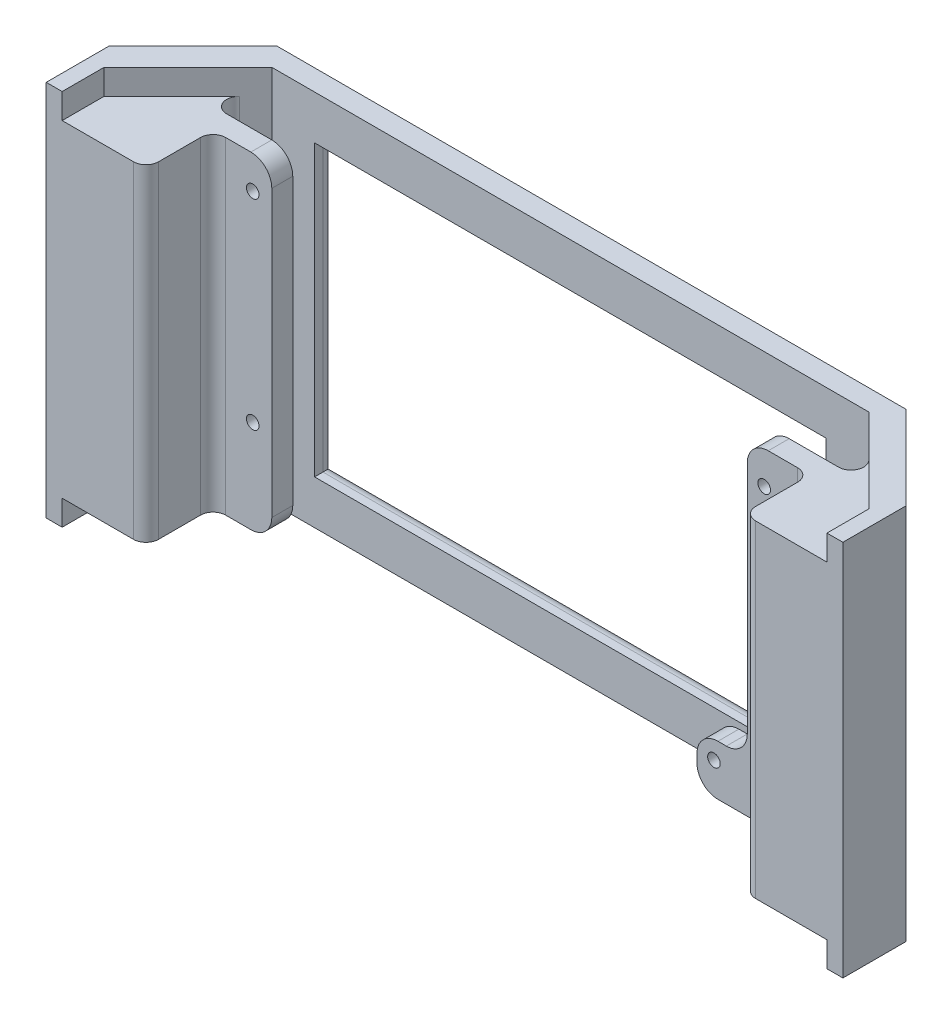
SolidWorks part; units mm, degrees
ref_plane "Front Plane" through (0, 0, 0) normal (0, 0, 1) x (1, 0, 0)
ref_plane "Top Plane" through (0, 0, 0) normal (0, 1, 0) x (1, 0, 0)
ref_plane "Right Plane" through (0, 0, 0) normal (1, 0, 0) x (0, 0, -1)
sketch "Sketch1" plane through (0, 0, 0) normal (0, 0, 1) x (1, 0, 0)
  line L1 (-95, 45) -> (95, 45)
  line L2 (-95, 45) -> (-95, -45)
  line L3 (-95, -45) -> (95, -45)
  line L4 (95, 45) -> (95, -45)
  line L5 (-95, 45) -> (95, -45) construction
  line L6 (-95, -45) -> (95, 45) construction
  line L7 (-61, 34.5) -> (61, 34.5)
  line L8 (-61, 34.5) -> (-61, -34.5)
  line L9 (-61, -34.5) -> (61, -34.5)
  line L10 (61, 34.5) -> (61, -34.5)
  line L11 (-61, 34.5) -> (61, -34.5) construction
  line L12 (-61, -34.5) -> (61, 34.5) construction
  point P0 (0, 0)
  point P6 (0, 0)
  dimension "D1" = 122
  dimension "D2" = 190
  dimension "D3" = 69
  dimension "D4" = 90
extrude "Boss-Extrude1" add sketch "Sketch1" along normal blind 5
sketch "Sketch2" plane through (0, 0, 5) normal (0, 0, 1) x (1, 0, 0)
  line L0 (-95, -45) -> (95, -45) construction
  line L1 (-95, 45) -> (-91.2, 45)
  line L2 (-95, 45) -> (-95, -45)
  line L3 (-95, -45) -> (-91.2, -45)
  line L4 (-91.2, 45) -> (-91.2, -45)
  line L5 (0, 0) -> (0, 45) construction
  line L6 (95, 45) -> (-95, 45) construction
  line L7 (95, -45) -> (91.2, -45)
  line L8 (91.2, 45) -> (91.2, -45)
  line L9 (95, 45) -> (91.2, 45)
  line L10 (95, 45) -> (95, -45)
  dimension "D1" = 3.8
extrude "Boss-Extrude2" add sketch "Sketch2" along normal blind 30
sketch "Sketch3" plane through (0, 45, 0) normal (0, 1, 0) x (1, 0, 0)
  line L0 (-91.2, -35) -> (-91.2, -5) construction
  line L1 (-91.2, -14) -> (-57.2, -14)
  line L2 (-91.2, -14) -> (-91.2, -19)
  line L3 (-91.2, -19) -> (-57.2, -19)
  line L4 (-57.2, -14) -> (-57.2, -19)
  line L5 (91.2, -35) -> (91.2, -5) construction
  line L6 (91.2, -14) -> (44.2, -14)
  line L7 (91.2, -14) -> (91.2, -19)
  line L8 (91.2, -19) -> (44.2, -19)
  line L9 (44.2, -14) -> (44.2, -19)
  line L10 (91.2, -5) -> (-91.2, -5) construction
  dimension "D1" = 9
  dimension "D2" = 9
  dimension "D3" = 5
  dimension "D4" = 5
  dimension "D5" = 34
  dimension "D6" = 47
extrude "Boss-Extrude3" add sketch "Sketch3" against normal up to surface (90 mm away) up to face at (0, -45, 18.75)
sketch "Sketch4" plane through (0, 0, 19) normal (0, 0, 1) x (1, 0, 0)
  line L0 (91.2, -45) -> (91.2, 45) construction
  line L1 (-91.2, 45) -> (91.2, 45)
  line L2 (-91.2, 45) -> (-91.2, 39)
  line L3 (-91.2, 39) -> (91.2, 39)
  line L4 (91.2, 45) -> (91.2, 39)
  line L5 (0, 0) -> (-91.2, 0) construction
  line L6 (-91.2, -45) -> (-91.2, 45) construction
  line L7 (-91.2, -39) -> (91.2, -39)
  line L8 (91.2, -45) -> (91.2, -39)
  line L9 (-91.2, -45) -> (91.2, -45)
  line L10 (-91.2, -45) -> (-91.2, -39)
  dimension "D1" = 6
extrude "Cut-Extrude1" cut sketch "Sketch4" against normal blind 5
sketch "Sketch5" plane through (0, 0, 19) normal (0, 0, 1) x (1, 0, 0)
  line L0 (0, 0) -> (-61.75, 0) construction
  line L1 (-70.2, 37.38) -> (70.2, 37.38) construction
  line L2 (-70.2, 37.38) -> (-70.2, -37.38) construction
  line L3 (-70.2, -37.38) -> (70.2, -37.38) construction
  line L4 (70.2, 37.38) -> (70.2, -37.38) construction
  line L5 (-70.2, 37.38) -> (70.2, -37.38) construction
  line L6 (-70.2, -37.38) -> (70.2, 37.38) construction
  line L7 (-61.75, 0) -> (-61.75, 31.13) construction
  line L8 (-61.75, 0) -> (-61.75, -16.61) construction
  line L9 (48.25, 0) -> (60.23, 0) construction
  line L10 (60.23, 0) -> (60.23, 31.13) construction
  line L11 (0, 0) -> (48.25, 0) construction
  line L12 (48.25, 0) -> (48.25, -31.38) construction
  circle A0 centre (-61.75, 31.13) radius 1.5
  circle A1 centre (-61.75, -16.61) radius 1.5
  circle A2 centre (60.23, 31.13) radius 1.5
  circle A3 centre (48.25, -31.38) radius 1.5
  point P0 (0, 0)
  dimension "D10" = 3
  dimension "D11" = 3
  dimension "D12" = 3
  dimension "D13" = 3
  dimension "D1" = 140.4
  dimension "D2" = 74.76
  dimension "D3" = 61.75
  dimension "D4" = 31.13
  dimension "D5" = 16.61
  dimension "D6" = 60.23
  dimension "D7" = 31.13
  dimension "D8" = 48.25
  dimension "D9" = 31.38
extrude "Cut-Extrude2" cut sketch "Sketch5" against normal up to surface (5 mm away) up to face at (67.7, 0, 14)
sketch "Sketch6" plane through (0, 0, 19) normal (0, 0, 1) x (1, 0, 0)
  line L1 (44.2, 39) -> (56.2, 39)
  line L2 (44.2, 39) -> (44.2, -27)
  line L3 (44.2, -27) -> (56.2, -27)
  line L4 (56.2, 39) -> (56.2, -27)
  dimension "D1" = 12
  dimension "D2" = 66
extrude "Cut-Extrude3" cut sketch "Sketch6" against normal up to surface (5 mm away) up to face at (46.75, -31.38, 14)
fillet "Fillet3" radius 3 4 edges at (-61, 0, 0) (0, -34.5, 0) (61, 0, 0) (0, 34.5, 0)
chamfer "Chamfer6" distance 20 angle 45 4 edges at (91.2, 0, 5) (95, 0, 0) (-95, 0, 0) (-91.2, 0, 5)
sketch "Sketch7" plane through (0, 39, 0) normal (0, 1, 0) x (1, 0, 0)
  line L0 (-85.2, -19) -> (-91.2, -25)
  line L1 (-91.2, -25) -> (-91.2, -35)
  line L2 (-91.2, -35) -> (-71.2, -35)
  line L3 (-71.2, -35) -> (-71.2, -19)
  line L4 (-85.2, -19) -> (-57.2, -19) construction
  line L5 (-71.2, -19) -> (-85.2, -19)
  line L6 (0, 0) -> (0, -5) construction
  line L7 (71.2, -5) -> (-71.2, -5) construction
  line L8 (71.2, -35) -> (71.2, -19)
  line L9 (91.2, -35) -> (71.2, -35)
  line L10 (91.2, -25) -> (91.2, -35)
  line L11 (85.2, -19) -> (91.2, -25)
  line L12 (71.2, -19) -> (85.2, -19)
  dimension "D1" = 20
extrude "Boss-Extrude4" add sketch "Sketch7" against normal up to surface (78 mm away) up to face at (-69.95, -39, 16.5)
fillet "Fillet4" radius 5 6 edges at (-57.2, -39, 16.5) (-57.2, 39, 16.5) (56.2, 39, 16.5) (44.2, -39, 16.5) (44.2, -27, 16.5) (56.2, -27, 16.5)
fillet "Fillet5" radius 3 4 edges at (-71.2, 0, 35) (71.2, 0, 35) (71.2, 0, 19) (-71.2, 0, 19)
fillet "Fillet6" radius 3 2 edges at (-80.2, 0, 14) (80.2, 0, 14)
